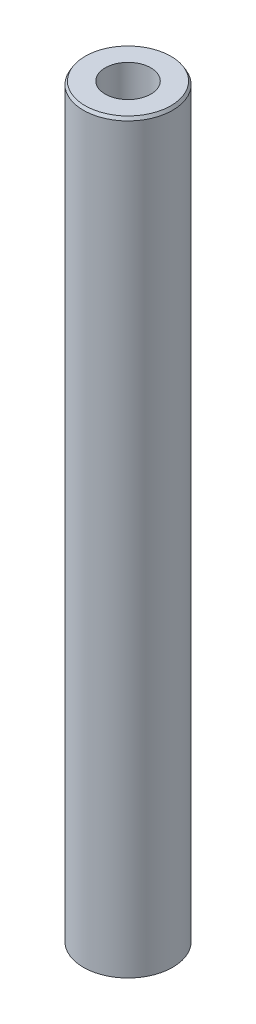
SolidWorks part; units mm, degrees
ref_plane "Front Plane" through (0, 0, 0) normal (0, 0, 1) x (1, 0, 0)
ref_plane "Top Plane" through (0, 0, 0) normal (0, 1, 0) x (1, 0, 0)
ref_plane "Right Plane" through (0, 0, 0) normal (1, 0, 0) x (0, 0, -1)
sketch "Sketch1" plane through (0, 0, 0) normal (0, 1, 0) x (1, 0, 0)
  circle A0 centre (0, 0) radius 10
  dimension "SHAFT_OD" = 20
extrude "Boss-Extrude1" add sketch "Sketch1" along normal blind 167.3409
sketch "Sketch2" plane through (0, 0, 0) normal (0, 1, 0) x (1, 0, 0)
  circle A0 centre (0, 0) radius 5.1139
  dimension "BORE_D" = 10.2278
extrude "Cut-Extrude1" cut sketch "Sketch2" along normal through all
chamfer "Chamfer1" distance 0.6852 angle 30 2 edges at (0, 167.3409, 10) (0, 0, 10) first distance on face at (0, 167.3409, 10) first distance on face at (0, 0, 5.1139)
